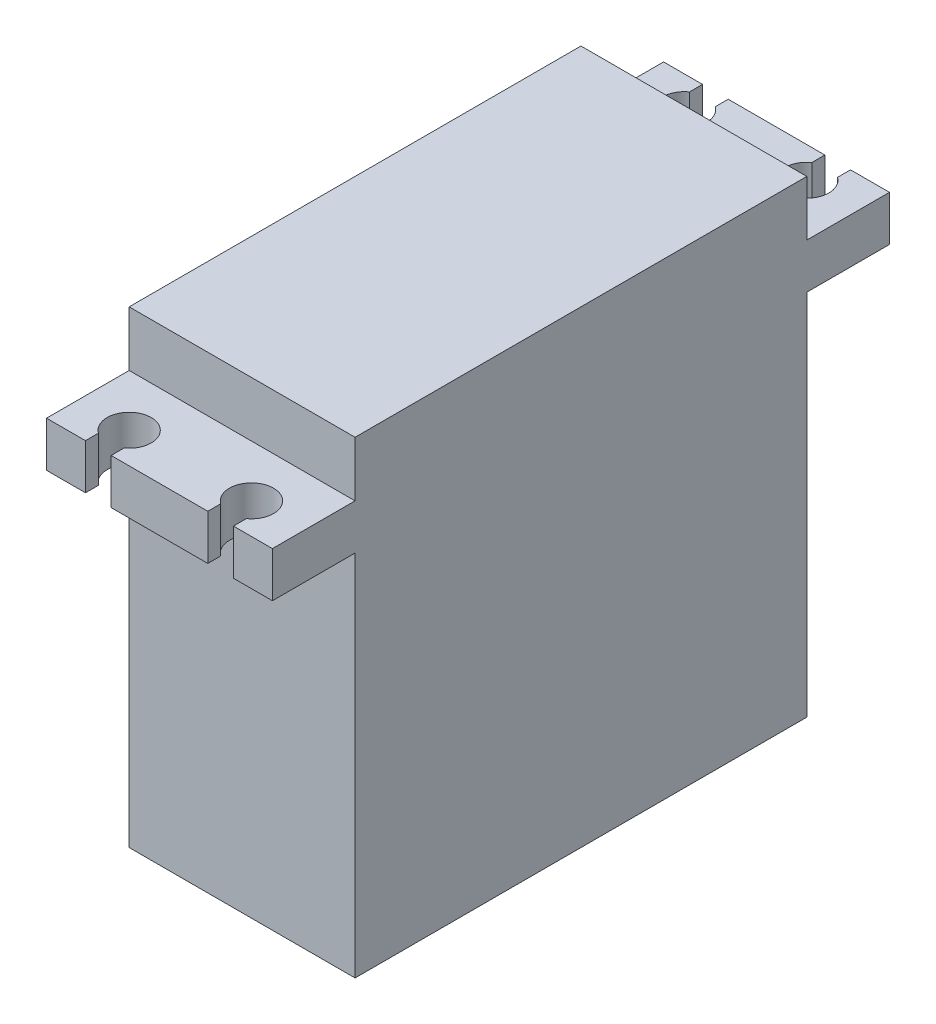
SolidWorks part; units mm, degrees
ref_plane "Front" through (0, 0, 0) normal (0, 0, 1) x (1, 0, 0)
ref_plane "Top" through (0, 0, 0) normal (0, 1, 0) x (1, 0, 0)
ref_plane "Right" through (0, 0, 0) normal (1, 0, 0) x (0, 0, -1)
sketch "Sketch2" plane through (0, 0, 0) normal (0, 1, 0) x (1, 0, 0)
  line L0 (-10.25, 20.5) -> (-10.25, 28)
  line L1 (-10.25, 20.5) -> (10.25, 20.5)
  line L2 (-10.25, 20.5) -> (-10.25, -20.5)
  line L3 (-10.25, -20.5) -> (10.25, -20.5)
  line L4 (10.25, 20.5) -> (10.25, -20.5)
  line L5 (-10.25, 20.5) -> (10.25, -20.5) construction
  line L6 (-10.25, -20.5) -> (10.25, 20.5) construction
  line L7 (-10.25, 28) -> (-6.715, 28)
  line L8 (10.25, 28) -> (10.25, 20.5)
  line L9 (-10.25, -20.5) -> (-10.25, -28)
  line L10 (-10.25, -28) -> (-6.715, -28)
  line L11 (10.25, -28) -> (10.25, -20.5)
  line L12 (0, 28) -> (0, -28) construction
  line L13 (-10.25, 0) -> (10.25, 0) construction
  line L14 (-4.385, 28) -> (4.385, 28)
  line L16 (-6.715, 28) -> (-6.715, 26.8257)
  line L18 (-4.385, 28) -> (-4.385, 26.8257)
  line L19 (4.385, 28) -> (4.385, 26.8257)
  line L20 (6.715, 28) -> (6.715, 26.8257)
  line L21 (6.715, 28) -> (10.25, 28)
  line L22 (6.715, -28) -> (6.715, -26.8257)
  line L23 (4.385, -28) -> (4.385, -26.8257)
  line L24 (-4.385, -28) -> (-4.385, -26.8257)
  line L25 (-6.715, -28) -> (-6.715, -26.8257)
  line L26 (-4.385, -28) -> (4.385, -28)
  line L27 (6.715, -28) -> (10.25, -28)
  arc A0 (-6.715, 26.8257) -> (-4.385, 26.8257) centre (-5.55, 25.2) ccw
  arc A1 (6.715, 26.8257) -> (4.385, 26.8257) centre (5.55, 25.2) cw
  arc A2 (6.715, -26.8257) -> (4.385, -26.8257) centre (5.55, -25.2) ccw
  arc A3 (-6.715, -26.8257) -> (-4.385, -26.8257) centre (-5.55, -25.2) cw
  point P0 (0, 0)
  point P15 (-6.8398, 26.7285)
  point P20 (0, 0)
  point P21 (-4.9501, 27.1079)
  point P37 (1.9649, 26.8257)
  point P38 (0, -28)
  point P39 (0, 28)
  dimension "D7" = 4
  dimension "D1" = 20.5
  dimension "D2" = 41
  dimension "D3" = 7.5
  dimension "D5" = 4.7
  dimension "D6" = 4.7
  dimension "D8" = 2.33
extrude "Boss-Extrude1" add sketch "Sketch2" along normal blind 42.5 contours L4 L1 L2 L3 region at (0, 0, 0)
extrude "Boss-Extrude2" add sketch "Sketch2<3>" along normal blind 4.1 from offset 33.4 contours L10 L11 L3 L9 | L8 L7 L0 L1 region at (0, 0, -23.9448) region at (0, 0, 23.9448)
sketch "Sketch2<3>" plane through (0, 0, 0) normal (0, 1, 0) x (1, 0, 0) same geometry as "Sketch2"
